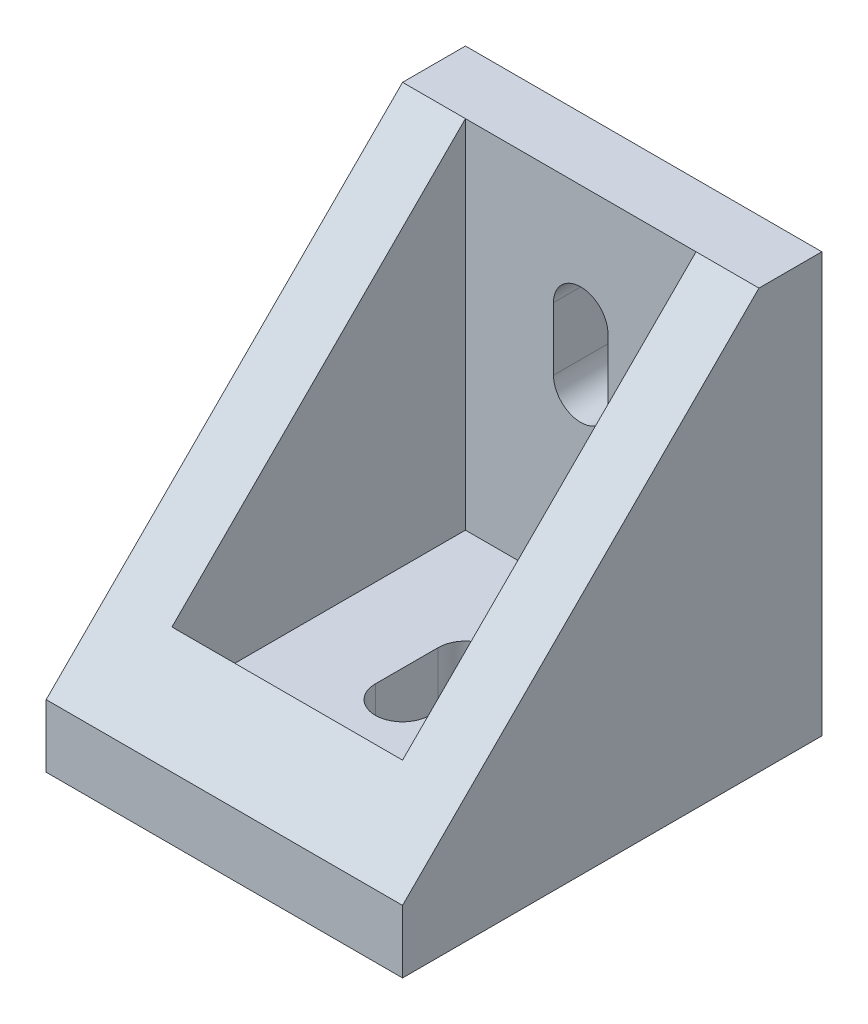
SolidWorks part; units mm, degrees
ref_plane "Front" through (0, 0, 0) normal (0, 0, 1) x (1, 0, 0)
ref_plane "Top" through (0, 0, 0) normal (0, 1, 0) x (1, 0, 0)
ref_plane "Right" through (0, 0, 0) normal (1, 0, 0) x (0, 0, -1)
sketch "Sketch1" plane through (0, 0, 0) normal (0, 1, 0) x (1, 0, 0)
  line L1 (-8.5, 10) -> (8.5, 10)
  line L2 (-8.5, 10) -> (-8.5, -10)
  line L3 (-8.5, -10) -> (8.5, -10)
  line L4 (8.5, 10) -> (8.5, -10)
  line L5 (-8.5, 10) -> (8.5, -10) construction
  line L6 (-8.5, -10) -> (8.5, 10) construction
  point P0 (0, 0)
  dimension "D1" = 17
  dimension "D2" = 20
extrude "Boss-Extrude1" add sketch "Sketch1" along normal blind 20
shell "Shell1" thickness 3 removed face at (0, 20, 0)
sketch "Sketch3" plane through (8.5, 0, 0) normal (1, 0, 0) x (0, 0, -1)
  line L0 (7, 20) -> (-10, 20)
  line L1 (-10, 20) -> (10, 20) construction
  line L2 (-10, 20) -> (-10, 3)
  line L3 (-10, 20) -> (-10, 0) construction
  line L4 (-10, 3) -> (7, 20)
  line L5 (-10, 0) -> (10, 0) construction
  dimension "D1" = 3
  dimension "D2" = 3
extrude "Cut-Extrude1" cut sketch "Sketch3" against normal through all
sketch "Sketch4" plane through (0, 3, 0) normal (0, 1, 0) x (1, 0, 0)
  line L0 (0, 1.5) -> (0, -1.5) construction
  line L1 (1.3, 1.5) -> (1.3, -1.5)
  line L2 (-1.3, 1.5) -> (-1.3, -1.5)
  line L5 (-4.3997, 7) -> (-4.3997, -7) construction
  line L6 (5.5, 7) -> (-5.5, 7) construction
  line L7 (-5.5, -7) -> (5.5, -7) construction
  arc A0 (1.3, 1.5) -> (-1.3, 1.5) centre (0, 1.5) ccw
  arc A1 (-1.3, -1.5) -> (1.3, -1.5) centre (0, -1.5) ccw
  point P2 (0, 0)
  point P8 (-4.3997, 0)
  dimension "D1" = 3
  dimension "D2" = 1.3
extrude "Cut-Extrude2" cut sketch "Sketch4" against normal through all
sketch "Sketch5" plane through (0, 0, -7) normal (0, 0, 1) x (1, 0, 0)
  line L0 (0, 14.5) -> (0, 11.5) construction
  line L1 (1.3, 14.5) -> (1.3, 11.5)
  line L2 (-1.3, 14.5) -> (-1.3, 11.5)
  line L3 (4.0251, 20) -> (4.0251, 6) construction
  line L4 (5.5, 20) -> (-5.5, 20) construction
  line L5 (5.5, 6) -> (-5.5, 6) construction
  arc A0 (1.3, 14.5) -> (-1.3, 14.5) centre (0, 14.5) ccw
  arc A1 (-1.3, 11.5) -> (1.3, 11.5) centre (0, 11.5) ccw
  point P3 (0, 13)
  point P14 (4.0251, 13)
  dimension "D1" = 3
  dimension "D2" = 1.3
extrude "Cut-Extrude3" cut sketch "Sketch5" against normal through all
